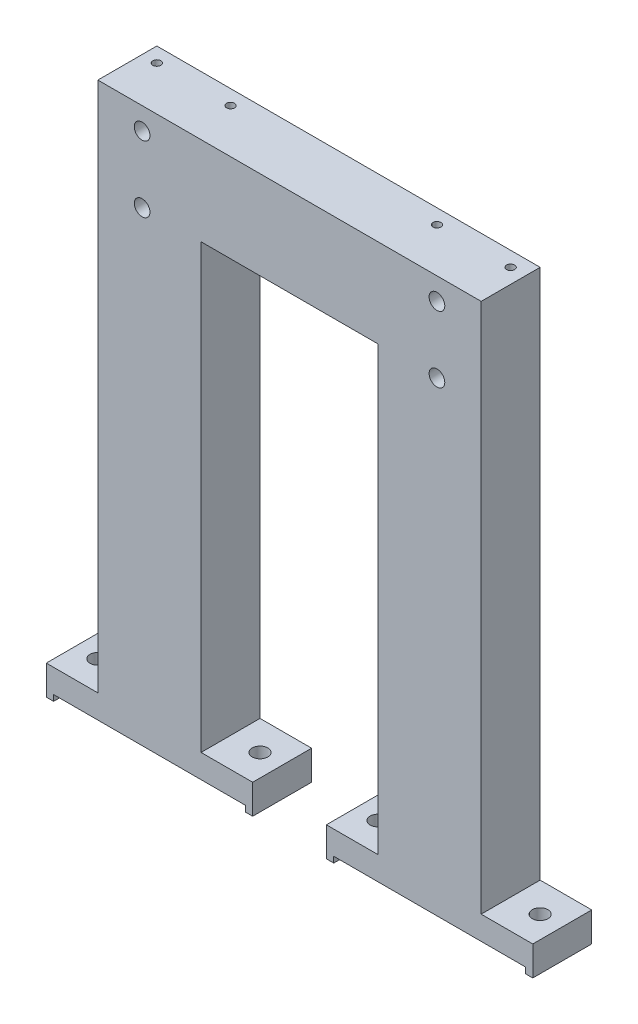
SolidWorks part; units mm, degrees
material "6061 Alloy"
ref_plane "Front Plane" through (0, 0, 0) normal (0, 0, 1) x (1, 0, 0)
ref_plane "Top Plane" through (0, 0, 0) normal (0, 1, 0) x (1, 0, 0)
ref_plane "Right Plane" through (0, 0, 0) normal (1, 0, 0) x (0, 0, -1)
sketch "Sketch1" plane through (0, 0, 0) normal (0, 0, 1) x (1, 0, 0)
  line L1 (-82.55, -120.65) -> (82.55, -120.65)
  line L2 (-82.55, -120.65) -> (-82.55, 120.65)
  line L3 (-82.55, 120.65) -> (82.55, 120.65)
  line L4 (82.55, -120.65) -> (82.55, 120.65)
  line L5 (-82.55, -120.65) -> (82.55, 120.65) construction
  line L6 (-82.55, 120.65) -> (82.55, -120.65) construction
  point P0 (0, 0)
  dimension "D1" = 241.3
  dimension "D2" = 165.1
extrude "Boss-Extrude1" add sketch "Sketch1" along normal blind 25.4
sketch "Sketch2" plane through (0, 0, 25.4) normal (0, 0, 1) x (1, 0, 0)
  line L0 (-82.55, -120.65) -> (82.55, -120.65) construction
  line L1 (-38.1, -120.65) -> (38.1, -120.65)
  line L2 (-38.1, -120.65) -> (-38.1, 82.55)
  line L3 (-38.1, 82.55) -> (38.1, 82.55)
  line L4 (38.1, -120.65) -> (38.1, 82.55)
  line L5 (-82.55, 120.65) -> (-82.55, -120.65) construction
  line L6 (82.55, 120.65) -> (-82.55, 120.65) construction
  dimension "D1" = 203.2
  dimension "D2" = 76.2
  dimension "D3" = 44.45
  dimension "D4" = 38.1
extrude "Cut-Extrude1" cut sketch "Sketch2" against normal through all
sketch "Sketch7" plane through (0, 0, 25.4) normal (0, 0, 1) x (1, 0, 0)
  line L0 (-82.55, -120.65) -> (-38.1, -120.65) construction
  line L1 (-104.775, -107.95) -> (-15.875, -107.95)
  line L2 (-104.775, -107.95) -> (-104.775, -120.65)
  line L3 (-104.775, -120.65) -> (-15.875, -120.65)
  line L4 (-15.875, -107.95) -> (-15.875, -120.65)
  line L5 (-104.775, -107.95) -> (-15.875, -120.65) construction
  line L6 (-104.775, -120.65) -> (-15.875, -107.95) construction
  line L7 (-82.55, 120.65) -> (-82.55, -120.65) construction
  point P0 (-60.325, -114.3)
  dimension "D1" = 0
  dimension "D2" = 88.9
  dimension "D3" = 22.225
  dimension "D4" = 12.7
extrude "Boss-Extrude4" add sketch "Sketch7" against normal blind 25.4
sketch "Sketch8" plane through (0, -120.65, 0) normal (0, -1, 0) x (-1, 0, 0)
  line L0 (104.775, -25.4) -> (15.875, -25.4) construction
  line L1 (101.6, 0) -> (19.05, 0)
  line L2 (101.6, 0) -> (101.6, -25.4)
  line L3 (101.6, -25.4) -> (19.05, -25.4)
  line L4 (19.05, 0) -> (19.05, -25.4)
  line L5 (101.6, 0) -> (19.05, -25.4) construction
  line L6 (101.6, -25.4) -> (19.05, 0) construction
  line L8 (104.775, 0) -> (104.775, -25.4) construction
  line L9 (15.875, 0) -> (15.875, -25.4) construction
  point P0 (60.325, -12.7)
  dimension "D1" = 25.4
  dimension "D2" = 3.175
  dimension "D3" = 3.175
extrude "Cut-Extrude4" cut sketch "Sketch8" against normal blind 2.54
mirror "Mirror3" about plane through (0, 0, 0) normal (1, 0, 0) of "Cut-Extrude4", "Boss-Extrude4"
hole_wizard "1/4 Clearance Hole1" positions "Sketch12" profile "Sketch13" hole size "1/4" standard "ANSI Inch" end condition up to next
sketch "Sketch12" plane through (0, -107.95, 0) normal (0, 1, 0) x (1, 0, 0)
  line L0 (-104.775, 0) -> (-104.775, -25.4) construction
  line L1 (-82.55, 0) -> (-104.775, 0) construction
  line L2 (-15.875, 0) -> (-38.1, 0) construction
  line L3 (-15.875, 0) -> (-15.875, -25.4) construction
  line L4 (15.875, 0) -> (15.875, -25.4) construction
  line L5 (15.875, 0) -> (38.1, 0) construction
  line L6 (82.55, 0) -> (104.775, 0) construction
  line L7 (104.775, 0) -> (104.775, -25.4) construction
  point P0 (-95.25, -12.7)
  point P2 (-25.4, -12.7)
  point P4 (25.4, -12.7)
  point P6 (95.25, -12.7)
  dimension "D1" = 9.525
  dimension "D2" = 12.7
  dimension "D3" = 12.7
  dimension "D4" = 9.525
  dimension "D5" = 9.525
  dimension "D6" = 12.7
  dimension "D7" = 12.7
  dimension "D8" = 9.525
sketch "Sketch13" plane through (-95.25, -107.95, 12.7) normal (1, 0, 0) x (0, 0, 1)
  line L0 (0, 0) -> (0, 10.16)
  line L1 (0, 10.16) -> (3.3782, 10.16)
  line L2 (3.3782, 10.16) -> (3.3782, 0)
  line L5 (3.3782, 0) -> (0, 0)
  line L11 (0, -6.35) -> (0, 107.95) construction
  dimension "Thru Hole Dia." = 6.7564
  dimension "Thru Hole Depth" = 10.16
hole_wizard "CBORE for 1/4 Socket Head Cap Screw1" positions "Sketch20" profile "Sketch21" counterbore size "1/4" standard "ANSI Inch" end condition through all
sketch "Sketch20" plane through (0, 0, 0) normal (0, 0, -1) x (-1, 0, 0)
  line L0 (-82.55, 120.65) -> (82.55, 120.65) construction
  line L1 (-82.55, -107.95) -> (-82.55, 120.65) construction
  line L2 (82.55, 120.65) -> (82.55, -107.95) construction
  point P0 (-63.5, 111.125)
  point P2 (-63.5, 82.55)
  point P4 (63.5, 111.125)
  point P6 (63.5, 82.55)
  dimension "D1" = 9.525
  dimension "D2" = 28.575
  dimension "D3" = 9.525
  dimension "D4" = 28.575
  dimension "D5" = 19.05
  dimension "D6" = 19.05
  dimension "D7" = 19.05
  dimension "D8" = 19.05
sketch "Sketch21" plane through (63.5, 111.125, 0) normal (1, 0, 0) x (0, 1, 0)
  line L0 (0, 0) -> (0, 25.4)
  line L1 (0, 25.4) -> (3.3782, 25.4)
  line L3 (3.3782, 25.4) -> (3.3782, 6.35)
  line L4 (3.3782, 6.35) -> (5.5562, 6.35)
  line L5 (5.5562, 6.35) -> (5.5562, 0)
  line L7 (5.5562, 0) -> (0, 0)
  line L11 (0, -6.35) -> (0, 107.95) construction
  dimension "Thru Hole Dia." = 6.7564
  dimension "Thru Hole Depth" = 25.4
  dimension "C'Bore Dia." = 11.1125
  dimension "C'Bore Depth" = 6.35
hole_wizard "#8-32 Tapped Hole1" positions "Sketch22" profile "Sketch23" tap size "#8-32" standard "ANSI Inch"
sketch "Sketch22" plane through (0, 120.65, 0) normal (0, 1, 0) x (1, 0, 0)
  line L0 (-82.55, -25.4) -> (-82.55, 0) construction
  line L1 (82.55, -25.4) -> (82.55, 0) construction
  line L2 (82.55, -25.4) -> (-82.55, -25.4) construction
  point P0 (-76.2, -6.35)
  point P2 (-44.45, -6.35)
  point P4 (44.45, -6.35)
  point P6 (76.2, -6.35)
  dimension "D1" = 6.35
  dimension "D2" = 38.1
  dimension "D3" = 38.1
  dimension "D4" = 6.35
  dimension "D5" = 19.05
  dimension "D6" = 19.05
  dimension "D7" = 19.05
  dimension "D8" = 19.05
cosmetic thread "Hole Thread1" parameters "D1"=8.382, "D2"=4.1656
cosmetic thread "Hole Thread2" parameters "D1"=8.382, "D2"=4.1656
cosmetic thread "Hole Thread3" parameters "D1"=8.382, "D2"=4.1656
cosmetic thread "Hole Thread4" parameters "D1"=8.382, "D2"=4.1656
sketch "Sketch23" plane through (-76.2, 120.65, 6.35) normal (1, 0, 0) x (0, 0, 1)
  line L0 (0, 0) -> (0, 13.7378)
  line L1 (0, 13.7378) -> (1.7272, 12.7)
  line L2 (1.7272, 12.7) -> (1.7272, 0)
  line L5 (1.7272, 0) -> (0, 0)
  line L10 (0, 13.7378) -> (-1.7272, 12.7) construction
  line L11 (0, -6.35) -> (0, 107.95) construction
  dimension "Tap Drill Dia." = 3.4544
  dimension "Tap Drill Depth" = 12.7
  dimension "Drill Angle" = 118
